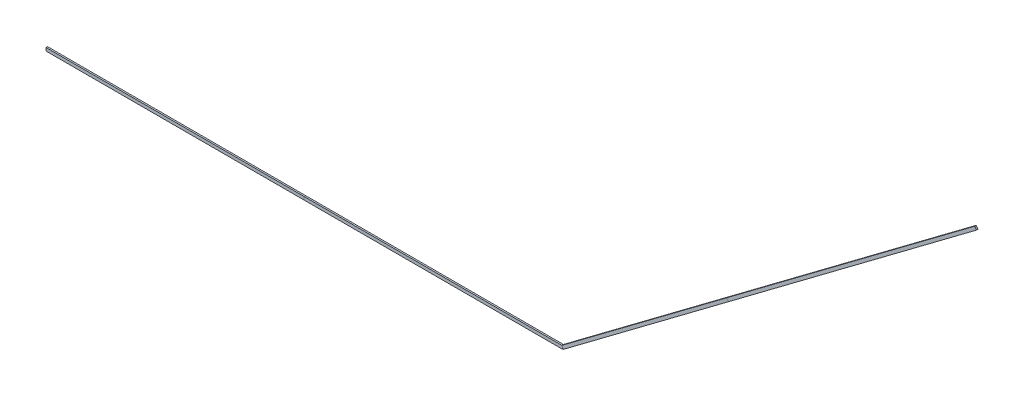
SolidWorks part; units mm, degrees
material "7075-T6 (SN)"
ref_plane "Front Plane" through (0, 0, 0) normal (0, 0, 1) x (1, 0, 0)
ref_plane "Top Plane" through (0, 0, 0) normal (0, 1, 0) x (1, 0, 0)
ref_plane "Right Plane" through (0, 0, 0) normal (1, 0, 0) x (0, 0, -1)
sketch "Sketch1" plane through (0, 0, 0) normal (0, 0, 1) x (1, 0, 0)
  line L2 (0, 0) -> (2500, 0)
  line L3 (2500, 0) -> (5000, 0)
  line L4 (5000, 0) -> (6600, 1200)
  line L5 (6600, 1200) -> (9000, 3000)
  point P7 (0, 0)
  point P9 (0, 0)
  point P10 (0, 0)
  dimension "D1" = 5000
  dimension "D2" = 3000
  dimension "D3" = 4000
  dimension "D4" = 3000
sketch "Sketch2" plane through (0, 0, 0) normal (1, 0, 0) x (0, 0, -1)
  line L1 (-7.5, -15) -> (7.5, -15)
  line L2 (-7.5, -15) -> (-7.5, 15)
  line L3 (-7.5, 15) -> (7.5, 15)
  line L4 (7.5, -15) -> (7.5, 15)
  line L5 (-7.5, -15) -> (7.5, 15) construction
  line L6 (-7.5, 15) -> (7.5, -15) construction
  point P0 (0, 0)
  dimension "D1" = 15
  dimension "D2" = 30
extrude "Boss-Extrude1" add sketch "Sketch2" along normal up to vertex (2500 mm away) up to point (2500, 0, 0)
extrude "Boss-Extrude9" add sketch "Sketch2<11>" along normal up to vertex (5000 mm away) from vertex separate body up to point (5000, 0, 0) starting at point (2500, 0, 0)
sketch "Sketch2<11>" plane through (0, 0, 0) normal (1, 0, 0) x (0, 0, -1) same geometry as "Sketch2"
ref_plane "Plane1" through (5000, 0, 0) normal (0.8, 0.6, 0) x (0, 0, -1)
sketch "Sketch3" plane through (5000, 0, 0) normal (0.8, 0.6, 0) x (0, 0, -1)
  line L1 (-7.5, -15) -> (7.5, -15)
  line L2 (-7.5, -15) -> (-7.5, 15)
  line L3 (-7.5, 15) -> (7.5, 15)
  line L4 (7.5, -15) -> (7.5, 15)
  line L5 (-7.5, -15) -> (7.5, 15) construction
  line L6 (-7.5, 15) -> (7.5, -15) construction
  point P0 (0, 0)
  point P5 (-29.009, -138.8722)
  dimension "D1" = 30
  dimension "D2" = 15
extrude "Boss-Extrude8" add sketch "Sketch3" along normal up to vertex (2000 mm away) separate body up to point (6600, 1200, 0)
extrude "Boss-Extrude10" add sketch "Sketch3<2>" along normal up to vertex (5000 mm away) from vertex separate body up to point (9000, 3000, 0) starting at point (6600, 1200, 0)
sketch "Sketch3<2>" plane through (5000, 0, 0) normal (0.8, 0.6, 0) x (0, 0, -1) same geometry as "Sketch3"
